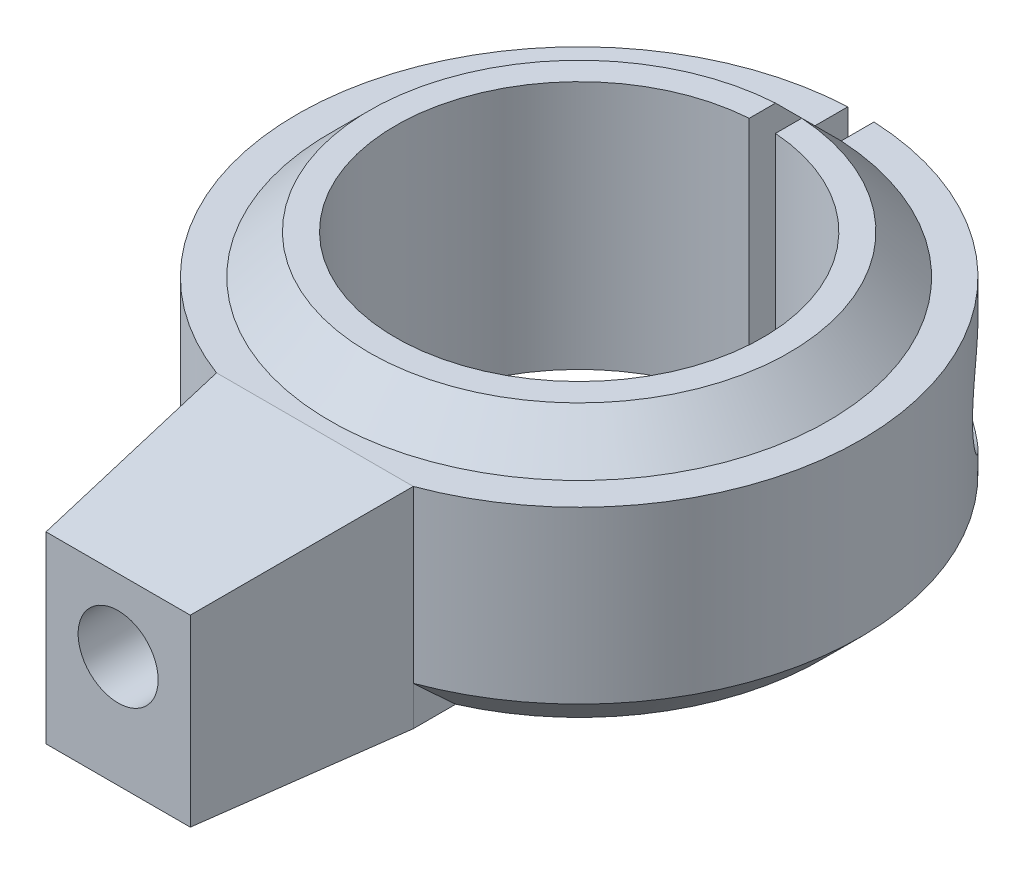
SolidWorks part; units mm, degrees
ref_plane "Front Plane" through (0, 0, 0) normal (0, 0, 1) x (1, 0, 0)
ref_plane "Top Plane" through (0, 0, 0) normal (0, 1, 0) x (1, 0, 0)
ref_plane "Right Plane" through (0, 0, 0) normal (1, 0, 0) x (0, 0, -1)
sketch "Sketch1" plane through (0, 0, 0) normal (0, 1, 0) x (1, 0, 0)
  line L0 (-16.7192, 17.9567) -> (-16.7192, 25.4692)
  line L2 (-23.2192, -16.1569) -> (-8.2192, -16.1569)
  line L3 (-23.2192, -16.1569) -> (-23.2192, -31.1569)
  line L4 (-23.2192, -31.1569) -> (-8.2192, -31.1569)
  line L5 (-8.2192, -16.1569) -> (-8.2192, -31.1569)
  line L9 (-16.7192, 25.4692) -> (-14.7192, 25.4692)
  line L10 (-14.7192, 25.4692) -> (-14.7192, 17.9567)
  circle A0 centre (-15.7192, 3.9925) radius 14
  circle A1 centre (-15.7192, 3.9925) radius 21.5
  dimension "D1" = 28
  dimension "D4" = 43
  dimension "D2" = 15
  dimension "D3" = 15
  dimension "D8" = 2
  dimension "D9" = 1
extrude "Boss-Extrude1" add sketch "Sketch1" along normal blind 16 contours A0 L0 L3 L10 | L3 L4 L5 L2 region at (-25.6664, 0, 6.6925)
sketch "Sketch2" plane through (0, 0, 31.1569) normal (0, 0, 1) x (1, 0, 0)
  line L0 (-23.2192, 0) -> (-8.2192, 0) construction
  circle A0 centre (-15.7192, 8.5) radius 3.05
  dimension "D1" = 6.1
  dimension "D2" = 8.5
extrude "Cut-Extrude1" cut sketch "Sketch2" against normal blind 15
sketch "Sketch3" plane through (0, 16, 0) normal (0, 1, 0) x (1, 0, 0)
  line L0 (-16.7192, 19.9612) -> (-16.7192, 17.9567)
  line L1 (-14.7192, 17.9567) -> (-14.7192, 19.9612)
  line L2 (-14.7192, 25.4692) -> (-14.7192, 17.9567) construction
  line L3 (-16.7192, 17.9567) -> (-16.7192, 25.4692) construction
  circle A0 centre (-15.7192, 3.9925) radius 16
  circle A1 centre (-15.7192, 3.9925) radius 12.25
  line M4 (-14.7192, 25.4692) -> (-14.7192, 17.9567)
  arc M5 (-14.7192, 17.9567) -> (-16.7192, 17.9567) centre (-15.7192, 3.9925) cw
  line M6 (-16.7192, 17.9567) -> (-16.7192, 25.4692)
  dimension "D1" = 32
extrude "Boss-Extrude2" add sketch "Sketch3" along normal blind 3 contours A0 M6 M4 M5 region at (-17.1715, 16, -18.959)
chamfer "Chamfer4" distance 3 angle 45 3 edges at (-15.7192, 16, 12.0075) (5.5234, 0, -7.3096) (-36.9618, 0, -7.3096)
chamfer "Chamfer6" distance 15 distance2 2 3 edges at (-8.2192, 8, 31.1569) (-15.7192, 16, 31.1569) (-23.2192, 8, 31.1569) first distance on face at (-8.2192, 6.7, 21.1856) first distance on face at (-15.7192, 16, 3.803) first distance on face at (-23.2192, 7.3, 21.8332)
sketch "Sketch4" plane through (-14.7192, 0, 0) normal (-1, 0, 0) x (0, 0, 1)
  line L0 (-22.4654, 0) -> (-17.9567, 0) construction
  line L2 (-25.4692, 16) -> (-25.4692, 3) construction
  circle A0 centre (-21.4692, 9) radius 1.5
  dimension "D1" = 3
  dimension "D2" = 9
  dimension "D3" = 4
extrude "Cut-Extrude2" cut sketch "Sketch4" against normal blind 25 and the other way blind 29
ref_plane "Plane1" through (5.7808, 0, 0) normal (1, 0, 0) x (0, 0, -1)
sketch "Sketch5" plane through (5.7808, 0, 0) normal (1, 0, 0) x (0, 0, -1)
  circle A0 centre (21.4692, 9) radius 2.5
  circle A1 centre (21.4692, 9) radius 5
  dimension "D1" = 5
  dimension "D2" = 10
extrude "Cut-Extrude3" cut sketch "Sketch5" against normal up to surface (20.5 mm away) contours A0 region at (5.7808, 9, -21.4692) up to face at (-14.7192, 9, -22.9692)
ref_plane "Plane2" through (-37.2192, 0, 0) normal (-1, 0, 0) x (0, 0, 1)
sketch "Sketch6" plane through (-37.2192, 0, 0) normal (-1, 0, 0) x (0, 0, 1)
  circle A0 centre (-21.4692, 9) radius 3
  circle A1 centre (-21.4692, 9) radius 5
  dimension "D1" = 6
  dimension "D2" = 10
extrude "Cut-Extrude4" cut sketch "Sketch6" against normal offset from surface (15.5 mm away) 5 contours A0 region at (-37.2192, 9, -21.4692) up to face at (-16.7192, 9, -19.9692)
extrude "Cut-Extrude5" cut sketch "Sketch5<3>" against normal blind 11
sketch "Sketch5<3>" plane through (5.7808, 0, 0) normal (1, 0, 0) x (0, 0, -1) same geometry as "Sketch5"
extrude "Cut-Extrude6" cut sketch "Sketch6<3>" against normal blind 11
sketch "Sketch6<3>" plane through (-37.2192, 0, 0) normal (-1, 0, 0) x (0, 0, 1) same geometry as "Sketch6"
fillet "Fillet1" radius 1 2 edges at (-5.2192, 9, -16.4692) (-26.2192, 9, -16.4692)
sketch "Sketch7" plane through (0, 0, 0) normal (0, -1, 0) x (1, 0, 0)
  line L1 (-21.2192, 31.1569) -> (-10.2192, 31.1569) construction
  circle A0 centre (-15.7192, 24.1569) radius 2.25
  dimension "D1" = 4.5
  dimension "D2" = 7
  dimension "D3" = 5.5
extrude "Cut-Extrude7" cut sketch "Sketch7" against normal up to surface (5.45 mm away) up to face at (-12.6692, 8.5, 16.1569)
